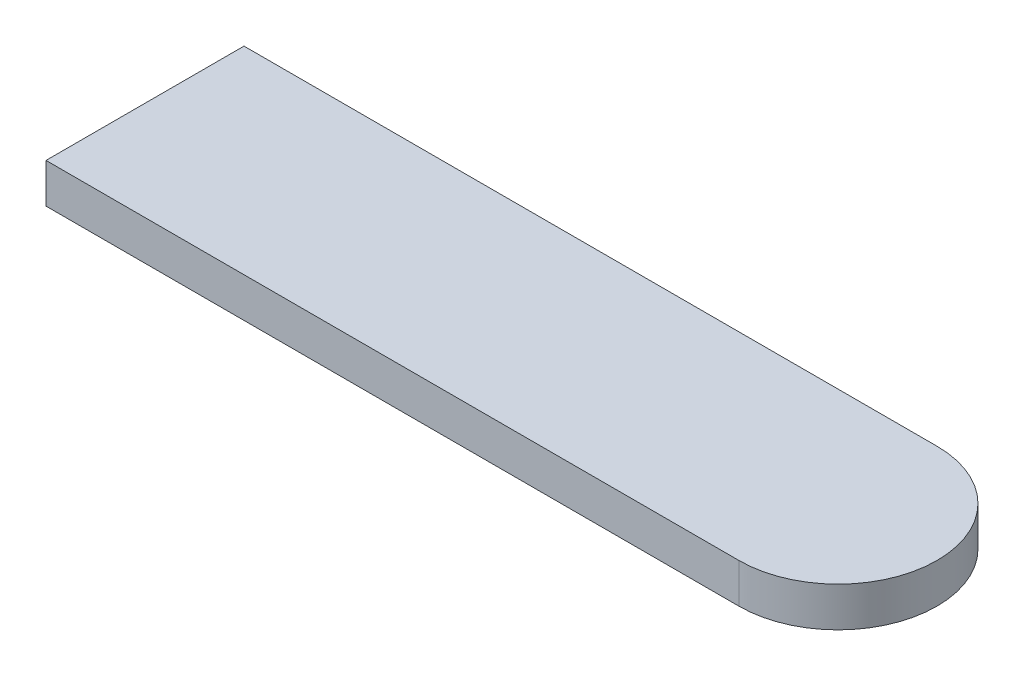
SolidWorks part; units mm, degrees
ref_plane "Plan de face" through (0, 0, 0) normal (0, 0, 1) x (1, 0, 0)
ref_plane "Plan de dessus" through (0, 0, 0) normal (0, 1, 0) x (1, 0, 0)
ref_plane "Plan de droite" through (0, 0, 0) normal (1, 0, 0) x (0, 0, -1)
sketch "Esquisse1" plane through (0, 0, 0) normal (0, 1, 0) x (1, 0, 0)
  line L0 (-100, -25) -> (75, -25)
  line L2 (-100, -25) -> (-100, 25)
  line L5 (-100, -25) -> (100, 25) construction
  line L6 (-100, 25) -> (100, -25) construction
  line L7 (-100, 25) -> (75, 25)
  arc A1 (75, -25) -> (75, 25) centre (75, 0) ccw
  point P0 (0, 0)
  dimension "D1" = 200
  dimension "D2" = 50
extrude "Boss.-Extru.1" add sketch "Esquisse1" along normal blind 10
